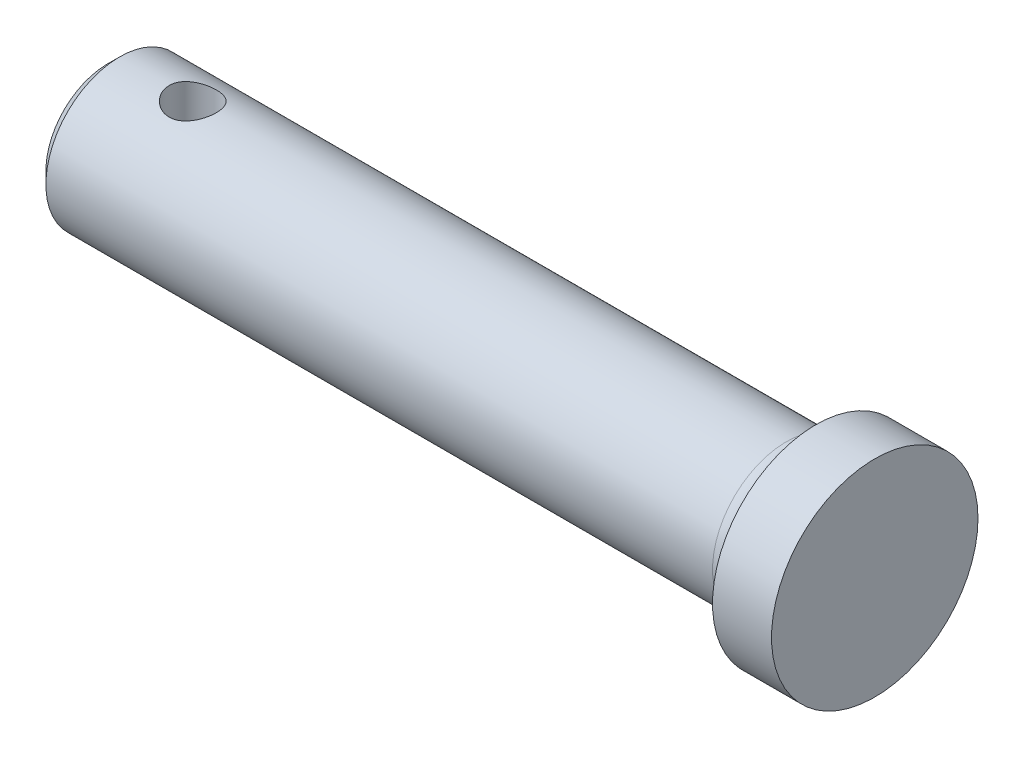
SolidWorks part; units mm, degrees
ref_plane "Front Plane" through (0, 0, 0) normal (0, 0, 1) x (1, 0, 0)
ref_plane "Top Plane" through (0, 0, 0) normal (0, 1, 0) x (1, 0, 0)
ref_plane "Right Plane" through (0, 0, 0) normal (1, 0, 0) x (0, 0, -1)
sketch "Sketch1" plane through (0, 0, 0) normal (1, 0, 0) x (0, 0, -1)
  circle A0 centre (0, 0) radius 1.25
  dimension "D1" = 2.5
extrude "Boss-Extrude1" add sketch "Sketch1" along normal blind 12
sketch "Sketch2" plane through (12, 0, 0) normal (1, 0, 0) x (0, 0, -1)
  circle A0 centre (0, 0) radius 1.75
  circle A1 centre (0, 0) radius 1.25 construction
  dimension "D1" = 0.5
extrude "Boss-Extrude2" add sketch "Sketch2" along normal blind 1
fillet "Fillet1" radius 0.5 1 edges at (12, 0, -1.25)
sketch "Sketch3" plane through (0, 0, 0) normal (0, 1, 0) x (1, 0, 0)
  line L0 (12, 0) -> (1.84, 0) construction
  line L2 (12, 1.75) -> (12, -1.75) construction
  circle A0 centre (1.44, 0) radius 0.4
  point P2 (10.9, 0)
  point P7 (0, 0)
  point P8 (0, 0)
  point P9 (0, 0)
  dimension "D2" = 0.8
  dimension "D1" = 10.16
extrude "Cut-Extrude1" cut sketch "Sketch3" against normal through all both and the other way through all
chamfer "Chamfer1" distance 0.2 angle 45 1 edges at (0, 0, -1.25)
